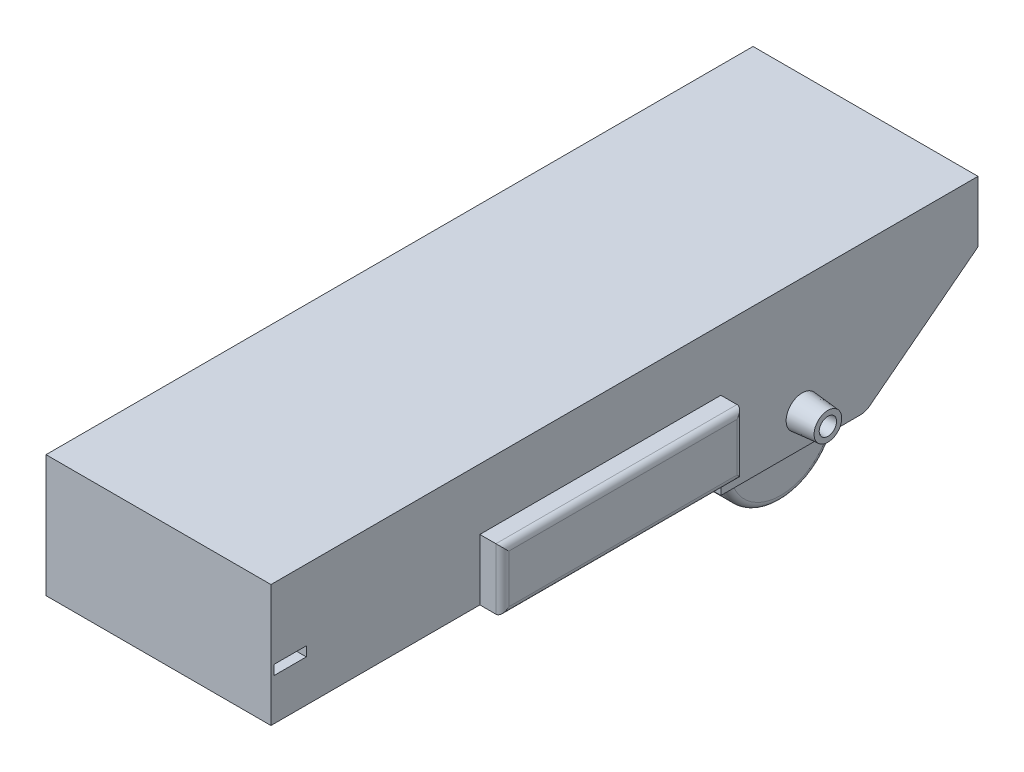
SolidWorks part; units mm, degrees
ref_plane "Front Plane" through (0, 0, 0) normal (0, 0, 1) x (1, 0, 0)
ref_plane "Top Plane" through (0, 0, 0) normal (0, 1, 0) x (1, 0, 0)
ref_plane "Right Plane" through (0, 0, 0) normal (1, 0, 0) x (0, 0, -1)
sketch "Sketch1" plane through (0, 0, 0) normal (0, 0, 1) x (1, 0, 0)
  line L1 (35, -19) -> (-35, -19)
  line L2 (35, -19) -> (35, 19)
  line L3 (35, 19) -> (-35, 19)
  line L4 (-35, -19) -> (-35, 19)
  line L5 (0, 19) -> (0, -19) construction
  line L6 (35, 0) -> (-35, 0) construction
  point P0 (0, 0)
  dimension "D1" = 70
  dimension "D2" = 38
extrude "Boss-Extrude1" add sketch "Sketch1" against normal blind 220
sketch "Sketch2" plane through (35, 0, 0) normal (1, 0, 0) x (0, 0, -1)
  line L0 (220, -19) -> (0, -19) construction
  line L2 (65, -19) -> (140, -19)
  line L3 (65, -19) -> (65, 0)
  line L4 (65, 0) -> (140, 0)
  line L5 (140, -19) -> (140, 0)
  line L6 (220, -19) -> (220, 19) construction
  dimension "D1" = 75
  dimension "D3" = 80
extrude "Boss-Extrude2" add sketch "Sketch2" along normal blind 7
mirror "Mirror1" about plane through (0, 0, 0) normal (1, 0, 0) of "Boss-Extrude2"
sketch "Sketch3" plane through (35, 0, 0) normal (1, 0, 0) x (0, 0, -1)
  line L0 (140, 0) -> (140, -27)
  line L1 (140, -27) -> (185, -27)
  line L2 (185, -27) -> (220, 0)
  line L3 (220, -19) -> (220, 19) construction
  line L4 (220, 0) -> (140, 0)
  line L5 (65, -19) -> (140, -19) construction
  dimension "D1" = 8
  dimension "D2" = 45
extrude "Boss-Extrude3" add sketch "Sketch3" against normal up to surface (70 mm away) up to face at (-35, -4.75, -106.25)
sketch "Sketch4" plane through (35, 0, 0) normal (1, 0, 0) x (0, 0, -1)
  line L0 (185, -27) -> (220, 0) construction
  line L1 (185, -27) -> (220, 0)
  line L2 (220, -19) -> (195.3704, -19) construction
  line L3 (220, -19) -> (220, 19) construction
  line L4 (220, -19) -> (195.3704, -19)
  line L5 (220, -19) -> (220, 19)
  line M6 (195.3704, -19) -> (220, -19)
  line M7 (220, -19) -> (220, 19)
extrude "Cut-Extrude1" cut sketch "Sketch4" against normal through all contours L1 M6 M7 region at (35, -12.6667, -211.7901)
fillet "Fillet1" radius 20 rebuild error yes
fillet "Fillet2" radius 5 1 edges at (0, -27, -185)
sketch "Sketch5" plane through (0, -27, 0) normal (0, -1, 0) x (1, 0, 0)
  line L0 (-35, -183.2955) -> (35, -183.2955) construction
  line L1 (28.3063, -183.2955) -> (13.3063, -183.2955)
  line L2 (28.3063, -183.2955) -> (28.3063, -165.2955)
  line L3 (28.3063, -165.2955) -> (13.3063, -165.2955)
  line L4 (13.3063, -183.2955) -> (13.3063, -165.2955)
  dimension "D1" = 18
  dimension "D2" = 15
revolve "Revolve1" add sketch "Sketch5" angle 180 about L3
fillet "Fillet3" radius 2 6 edges at (13.3063, -27, -165.2955) (20.8063, -27, -183.2955) (13.3063, -45, -165.2955) (20.8063, -27, -147.2955) (28.3063, -27, -165.2955) (28.3063, -45, -165.2955)
fillet "Fillet4" radius 2 8 edges at (-42, -19, -102.5) (-42, -9.5, -140) (-42, 0, -102.5) (-42, -9.5, -65) (42, 0, -102.5) (42, -9.5, -140) (42, -19, -102.5) (42, -9.5, -65)
sketch "Sketch6" plane through (35, 0, 0) normal (1, 0, 0) x (0, 0, -1)
  line L0 (165.2955, -29) -> (165.2955, -11.5578) construction
  line L1 (181.1701, -29) -> (149.421, -29) construction
  line L2 (140, -27) -> (183.2955, -27) construction
  circle A0 centre (165.2955, -17) radius 2
  dimension "D1" = 10
extrude "Cut-Extrude2" cut sketch "Sketch6" against normal up to surface (70 mm away) up to face at (-35, -9.0193, -123.6119)
sketch "Sketch7" plane through (35, 0, 0) normal (1, 0, 0) x (0, 0, -1)
  circle A0 centre (165.2955, -17) radius 2 construction
  circle A1 centre (165.2955, -17) radius 2
extrude "Extrude-Thin1" add sketch "Sketch7" along normal blind 8 draft 5 thin thin type one direction wall 3
mirror "Mirror2" about plane through (0, 0, 0) normal (1, 0, 0) of "Extrude-Thin1"
sketch "Sketch8" plane through (35, 0, 0) normal (1, 0, 0) x (0, 0, -1)
  line L0 (65, -19) -> (0, -19) construction
  line L1 (1, -3) -> (11, -3)
  line L2 (1, -3) -> (1, -6)
  line L3 (1, -6) -> (11, -6)
  line L4 (11, -3) -> (11, -6)
  line L5 (0, -19) -> (0, 19) construction
  dimension "D1" = 13
  dimension "D2" = 1
  dimension "D3" = 10
  dimension "D4" = 3
extrude "Cut-Extrude3" cut sketch "Sketch8" against normal through all
sketch "Sketch9" plane through (0, 19, 0) normal (0, 1, 0) x (1, 0, 0)
  line L0 (35, 220) -> (35, 0) construction
  line L1 (-35, 0) -> (35, 0)
  line L2 (-35, 0) -> (-35, 46)
  line L3 (-35, 46) -> (35, 46)
  line L4 (35, 0) -> (35, 46)
  dimension "D1" = 46
sketch "Sketch12" [suppressed] plane through (0, -29, 0) normal (0, -1, 0) x (1, 0, 0)
  line L0 (35, -140) -> (-35, -140) construction
  line L1 (-29, -140) -> (29, -140)
  line L2 (-29, -140) -> (-29, -45)
  line L3 (-29, -45) -> (29, -45)
  line L4 (29, -140) -> (29, -45)
  point P6 (0, -45)
  dimension "D1" = 58
  dimension "D2" = 95
extrude "Cut-Extrude6" [suppressed] cut sketch "Sketch12" against normal blind 28
sketch "Sketch13" [suppressed] plane through (-29, 0, 0) normal (1, 0, 0) x (0, 0, -1)
  line L0 (45, -29) -> (140, -29) construction
  line L1 (140, -1) -> (140, -29) construction
  circle A0 centre (138, -27) radius 0.5
  dimension "D1" = 2
  dimension "D3" = 1
  dimension "D2" = 2
extrude "Cut-Extrude7" [suppressed] cut sketch "Sketch13" against normal blind 1
mirror "Mirror3" [suppressed] about plane through (0, 0, 0) normal (1, 0, 0)
sketch "Sketch14" plane through (0, -19, 0) normal (0, -1, 0) x (1, 0, 0)
  line L0 (35, -140) -> (-35, -140) construction
  line L1 (-29, -140) -> (29, -140)
  line L2 (-29, -140) -> (-29, -45)
  line L3 (-29, -45) -> (29, -45)
  line L4 (29, -140) -> (29, -45)
  line L5 (-35, 0) -> (35, 0) construction
  point P6 (0, -45)
  point P9 (0, 0)
  dimension "D1" = 58
  dimension "D2" = 95
extrude "Cut-Extrude8" cut sketch "Sketch14" against normal blind 28
sketch "Sketch15" plane through (-29, 0, 0) normal (1, 0, 0) x (0, 0, -1)
  line L0 (140, 9) -> (140, -19) construction
  line L1 (45, -19) -> (140, -19) construction
  circle A0 centre (138, -17) radius 0.5
  dimension "D3" = 1
  dimension "D1" = 2
  dimension "D2" = 2
extrude "Cut-Extrude9" cut sketch "Sketch15" against normal blind 1
mirror "Mirror4" about plane through (0, 0, 0) normal (1, 0, 0) of "Cut-Extrude9"
sketch "Sketch16" plane through (0, -19, 0) normal (0, -1, 0) x (1, 0, 0)
  line L0 (29, -45) -> (-29, -45) construction
  circle A0 centre (-18.7616, -39.5) radius 1
  dimension "D1" = 5.5
extrude "Cut-Extrude10" cut sketch "Sketch16" against normal blind 1
sketch "Sketch17" plane through (0, -27, 0) normal (0, -1, 0) x (1, 0, 0)
  line L1 (-25.68, -149.6575) -> (-15.68, -149.6575)
  line L2 (-25.68, -149.6575) -> (-25.68, -155.6575)
  line L3 (-25.68, -155.6575) -> (-15.68, -155.6575)
  line L4 (-15.68, -149.6575) -> (-15.68, -155.6575)
  dimension "D1" = 6
  dimension "D2" = 10
extrude "Cut-Extrude11" cut sketch "Sketch17" against normal blind 4
sketch "Sketch18" plane through (0, -27, 0) normal (0, -1, 0) x (1, 0, 0)
  line L0 (-24.68, -150.6575) -> (-24.68, -154.6575)
  line L1 (-24.68, -154.6575) -> (-16.68, -154.6575)
  line L2 (-16.68, -154.6575) -> (-16.68, -150.6575)
  line L3 (-16.68, -150.6575) -> (-24.68, -150.6575)
  line L4 (-25.68, -149.6575) -> (-25.68, -155.6575)
  line L5 (-25.68, -155.6575) -> (-15.68, -155.6575)
  line L6 (-15.68, -155.6575) -> (-15.68, -149.6575)
  line L7 (-15.68, -149.6575) -> (-25.68, -149.6575)
  line L8 (-25.68, -149.6575) -> (-25.68, -155.6575)
  line L9 (-25.68, -155.6575) -> (-15.68, -155.6575)
  line L10 (-15.68, -155.6575) -> (-15.68, -149.6575)
  line L11 (-15.68, -149.6575) -> (-25.68, -149.6575)
  line L12 (-20.68, -150.6575) -> (-20.68, -154.6575)
  dimension "D1" = 0
  dimension "D2" = 1
extrude "Boss-Extrude5" add sketch "Sketch18" against normal blind 4 and the other way blind 2 contours L12 L3 L0 L1 region at (-22.68, -27, -152.6575)
fillet "Fillet5" radius 0.2 4 edges at (-22.68, -29, -154.6575) (-24.68, -29, -152.6575) (-22.68, -29, -150.6575) (-20.68, -29, -152.6575)
sketch "Sketch20" plane through (0, -29, 0) normal (0, -1, 0) x (1, 0, 0)
  line L0 (-22.68, -150.8575) -> (-22.68, -154.4575) construction
  line L1 (-20.88, -150.8575) -> (-24.48, -150.8575) construction
  line L2 (-24.48, -154.4575) -> (-20.88, -154.4575) construction
  line L3 (-22.93, -154.4575) -> (-22.93, -150.8575)
  line L4 (-22.93, -154.4575) -> (-22.43, -154.4575)
  line L5 (-22.93, -150.8575) -> (-22.43, -150.8575)
  line L6 (-22.43, -154.4575) -> (-22.43, -150.8575)
  line L7 (-22.93, -154.4575) -> (-22.43, -150.8575) construction
  line L8 (-22.93, -150.8575) -> (-22.43, -154.4575) construction
  line L9 (-21.63, -154.4575) -> (-21.63, -150.8575)
  line L10 (-22.13, -154.4575) -> (-21.63, -154.4575)
  line L11 (-22.13, -154.4575) -> (-22.13, -150.8575)
  line L12 (-22.13, -150.8575) -> (-21.63, -150.8575)
  line L13 (-20.83, -154.4575) -> (-20.83, -150.8575)
  line L14 (-21.33, -154.4575) -> (-20.83, -154.4575)
  line L15 (-21.33, -154.4575) -> (-21.33, -150.8575)
  line L16 (-21.33, -150.8575) -> (-20.83, -150.8575)
  line L17 (-23.23, -154.4575) -> (-23.23, -150.8575)
  line L18 (-23.73, -154.4575) -> (-23.23, -154.4575)
  line L19 (-23.73, -154.4575) -> (-23.73, -150.8575)
  line L20 (-23.73, -150.8575) -> (-23.23, -150.8575)
  line L21 (-24.03, -154.4575) -> (-24.03, -150.8575)
  line L22 (-24.53, -154.4575) -> (-24.03, -154.4575)
  line L23 (-24.53, -154.4575) -> (-24.53, -150.8575)
  line L24 (-24.53, -150.8575) -> (-24.03, -150.8575)
  point P7 (-22.68, -152.6575)
  point P8 (-22.68, -152.6575)
  dimension "D1" = 0.5
  dimension "D2" = 3
  dimension "D3" = 3
extrude "Cut-Extrude12" cut sketch "Sketch20" against normal blind 0.5
sketch "Sketch21" plane through (0, -27, 0) normal (0, -1, 0) x (1, 0, 0)
  text T0 "<b>ON</b>" font "Century Gothic" height 3.5
sketch "Sketch22" plane through (0, -27, 0) normal (0, -1, 0) x (1, 0, 0)
  text T0 "<b>OFF</b>"
extrude "Boss-Extrude7" add sketch "Sketch22" along normal blind 0.5
extrude "Boss-Extrude8" add sketch "Sketch21" along normal blind 0.5
